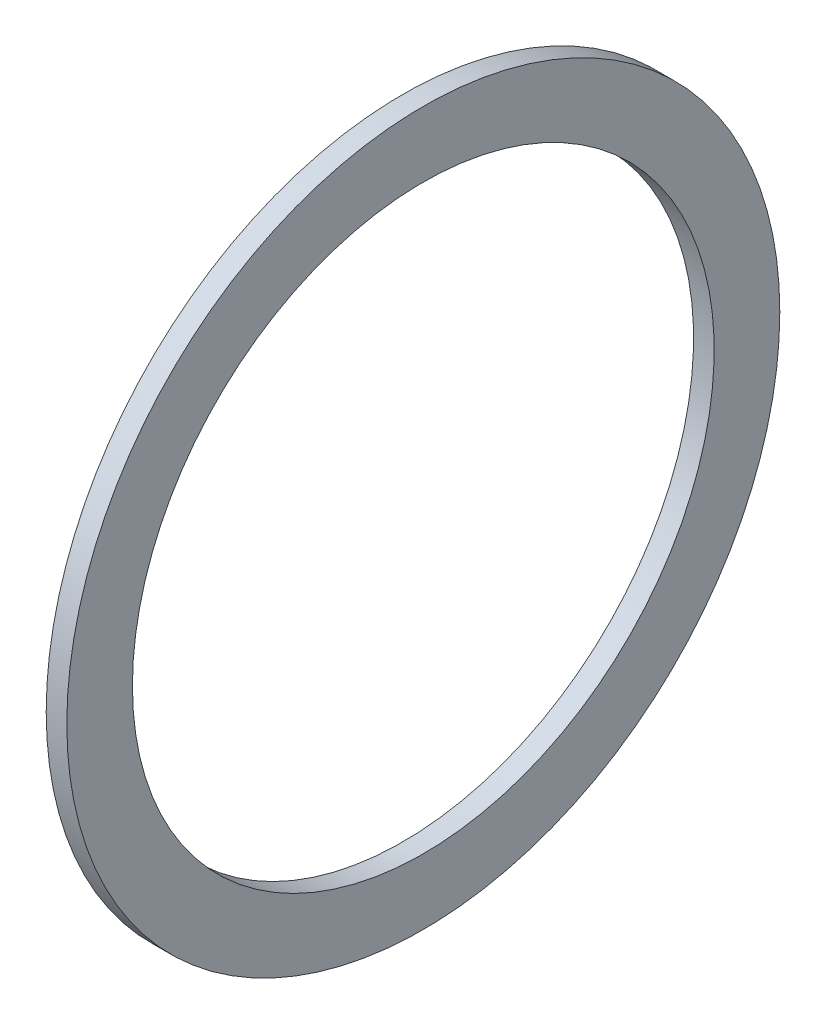
SolidWorks part; units mm, degrees
ref_plane "Front Plane" through (0, 0, 0) normal (0, 0, 1) x (1, 0, 0)
ref_plane "Top Plane" through (0, 0, 0) normal (0, 1, 0) x (1, 0, 0)
ref_plane "Right Plane" through (0, 0, 0) normal (1, 0, 0) x (0, 0, -1)
sketch "Sketch2" plane through (0, 0, 0) normal (0, 0, 1) x (1, 0, 0)
  line L0 (0, 0) -> (58.591, 0) construction
  line L2 (0, 0) -> (18.4, 0)
  line L3 (0, 0) -> (0, 2.5)
  line L4 (0, 2.5) -> (18.4, 2.5)
  line L5 (18.4, 0) -> (18.4, 2.5)
  line L6 (6.0094, 2.5) -> (6.0094, 6)
  line L11 (6.0094, 6) -> (9.9794, 6)
  line L16 (12.9794, 6) -> (12.9794, 3)
  line L17 (12.9794, 3) -> (13.6398, 3)
  line L18 (13.6398, 3) -> (13.6398, 2.5)
  line L19 (13.6398, 2.5) -> (6.0094, 2.5)
  line L22 (13.6398, 2.5) -> (16.1198, 2.5)
  line L23 (13.6398, 2.5) -> (13.6398, 4)
  line L24 (13.6398, 4) -> (16.1198, 4)
  line L25 (16.1198, 2.5) -> (16.1198, 4)
  line L27 (6.0094, 6) -> (9.9794, 6)
  line L28 (6.0094, 6) -> (6.0094, 9)
  line L29 (6.0094, 9) -> (9.9794, 9)
  line L30 (9.9794, 6) -> (9.9794, 9)
  line L31 (6.0094, 9) -> (6.0094, 8.25)
  line L32 (6.0094, 8.25) -> (5.0094, 8.25)
  line L33 (8.6609, 22.001) -> (8.6609, 12.476) construction
  line L34 (5.0094, 12.476) -> (12.3124, 12.476)
  line L35 (9.9794, 9) -> (12.3124, 9)
  line L36 (5.0094, 7.9375) -> (1.8344, 7.9375)
  line L37 (5.0094, 8.25) -> (5.0094, 12.476)
  line L38 (5.0094, 7.9375) -> (5.0094, 13.9365)
  line L39 (5.0094, 13.9365) -> (1.8344, 13.9365)
  line L40 (1.8344, 7.9375) -> (1.8344, 13.9365)
  line L41 (5.0094, 22.001) -> (12.3124, 22.001)
  line L42 (5.0094, 22.001) -> (5.0094, 30.1625)
  line L43 (5.0094, 30.1625) -> (12.3124, 30.1625)
  line L44 (12.3124, 22.001) -> (12.3124, 30.1625)
  line L49 (16.6398, 22.001) -> (16.6398, 7.5)
  line L51 (23.0198, 7.5) -> (23.0198, 6.5)
  line L54 (16.1198, 4) -> (13.6398, 4)
  line L56 (18.0398, 7.5) -> (23.0198, 7.5)
  line L57 (13.3124, 22.001) -> (16.6398, 22.001)
  line L58 (16.1198, 3.5) -> (20.0198, 3.5)
  line L59 (29.9098, 14) -> (26.9098, 11)
  line L60 (4.0094, 31.75) -> (18.0398, 31.75)
  line L61 (18.0398, 7.5) -> (23.0198, 7.5)
  line L62 (18.0398, 7.5) -> (18.0398, 12)
  line L63 (18.0398, 12) -> (23.0198, 12)
  line L64 (23.0198, 7.5) -> (23.0198, 12)
  line L65 (18.0398, 31.75) -> (18.0398, 12)
  line L66 (23.0198, 11) -> (26.9098, 11)
  line L67 (34.8098, 23) -> (31.3098, 19.5)
  line L68 (35.8098, 31) -> (38.7998, 33.99)
  line L69 (29.9098, 14) -> (29.9098, 15)
  line L70 (29.9098, 15) -> (22.9398, 15)
  line L71 (22.9398, 15) -> (21.0398, 15)
  line L72 (18.0398, 7.5) -> (16.6398, 7.5)
  line L73 (21.0398, 15) -> (21.0398, 43)
  line L74 (19.5798, 40) -> (9.6198, 40)
  line L75 (9.6198, 40) -> (4.0094, 40)
  line L76 (21.0398, 43) -> (19.5798, 43)
  line L77 (22.9398, 15) -> (29.9098, 15)
  line L78 (22.9398, 15) -> (22.9398, 21)
  line L79 (22.9398, 21) -> (29.9098, 21)
  line L80 (29.9098, 15) -> (29.9098, 21)
  line L81 (9.6198, 40) -> (19.5798, 40)
  line L82 (9.6198, 40) -> (9.6198, 50)
  line L83 (9.6198, 50) -> (19.5798, 50)
  line L84 (19.5798, 40) -> (19.5798, 50)
  line L85 (4.0094, 40) -> (4.0094, 31.75)
  line L86 (12.9794, 3) -> (12.9794, 2.5)
  line L87 (31.3098, 19.5) -> (29.9098, 19.5)
  line L88 (21.4694, 63.5) -> (21.4694, 51.308)
  line L89 (21.4694, 63.5) -> (25.9398, 63.5)
  line L90 (25.9398, 63.5) -> (25.9398, 25)
  line L91 (27.8398, 25) -> (25.9398, 25)
  line L92 (9.6198, 48) -> (8.1598, 48)
  line L93 (8.1598, 48) -> (8.1598, 53.476)
  line L94 (8.1598, 53.476) -> (19.5798, 53.476)
  line L95 (19.5798, 53.476) -> (19.5798, 50)
  line L96 (13.8698, 63.001) -> (13.8698, 53.476) construction
  line L97 (8.1598, 63.001) -> (19.5798, 63.001)
  line L98 (8.1598, 63.001) -> (8.1598, 68.2625)
  line L99 (8.1598, 68.2625) -> (19.5798, 68.2625)
  line L100 (19.5798, 63.001) -> (19.5798, 68.2625)
  line L101 (12.9794, 6) -> (11.9794, 6)
  line L102 (8.1598, 44.825) -> (4.9848, 44.825)
  line L103 (8.1598, 44.825) -> (8.1598, 54.9365)
  line L104 (8.1598, 54.9365) -> (4.9848, 54.9365)
  line L106 (9.9794, 6) -> (10.8794, 6)
  line L107 (27.8398, 25) -> (34.8098, 25)
  line L108 (34.8098, 25) -> (34.8098, 23)
  line L109 (0, 0) -> (-2, 0)
  line L110 (0, 0) -> (0, 11)
  line L111 (27.8398, 25) -> (34.8098, 25)
  line L112 (27.8398, 25) -> (27.8398, 32.5)
  line L113 (27.8398, 32.5) -> (34.8098, 32.5)
  line L114 (34.8098, 25) -> (34.8098, 32.5)
  line L115 (35.8098, 31) -> (34.8098, 31)
  line L116 (27.8398, 32.5) -> (27.8398, 64.5)
  line L117 (20.5373, 74.025) -> (6.2023, 74.025)
  line L118 (6.2023, 74.025) -> (6.2023, 76.2)
  line L119 (38.7998, 47.29) -> (30.8398, 55.25)
  line L120 (0, 11) -> (-2, 11)
  line L121 (38.7998, 43.815) -> (30.8623, 43.815)
  line L123 (-4.8152, 69.85) -> (1.5348, 76.2)
  line L124 (38.7998, 47.29) -> (38.7998, 33.99)
  line L125 (-2, 0) -> (-2, 11)
  line L126 (38.7998, 37.465) -> (30.8623, 37.465)
  line L127 (30.8623, 43.815) -> (30.8623, 37.465)
  line L128 (6.0094, 2.5) -> (6.0094, 0)
  line L129 (-0.0152, 63.5) -> (-0.0152, 30)
  line L132 (4.9848, 63.5) -> (-0.0152, 63.5)
  line L136 (-1.8152, 30) -> (-11.7752, 30)
  line L138 (-13.7752, 25.4) -> (-2, 25.4)
  line L139 (-2, 25.4) -> (-2, 11.5)
  line L140 (27.8398, 64.5) -> (20.5373, 64.5)
  line L141 (-1.8152, 30) -> (-11.7752, 30)
  line L142 (-1.8152, 30) -> (-1.8152, 39)
  line L143 (-1.8152, 39) -> (-11.7752, 39)
  line L144 (-11.7752, 30) -> (-11.7752, 39)
  line L145 (20.5373, 64.5) -> (20.5373, 74.025)
  line L146 (-12.7752, 37) -> (-12.7752, 47.29)
  line L147 (-12.7752, 37) -> (-11.7752, 37)
  line L148 (30.8398, 55.25) -> (30.8398, 76.2)
  line L149 (11.9794, 6) -> (11.9794, 5.45)
  line L154 (-2, 11.5) -> (0.5, 11.5)
  line L155 (4.9848, 60.6197) -> (24.0348, 60.6197)
  line L160 (4.9848, 60.6197) -> (4.9848, 55.8572)
  line L161 (4.9848, 55.8572) -> (24.0348, 55.8572)
  line L166 (24.0348, 60.6197) -> (24.0348, 55.8572)
  line L167 (4.9848, 60.6197) -> (24.0348, 55.8572) construction
  line L172 (4.9848, 55.8572) -> (24.0348, 60.6197) construction
  line L173 (24.0348, 62.2072) -> (25.9398, 62.2072)
  line L174 (11.9794, 5.45) -> (10.8794, 5.45)
  line L175 (10.8794, 6) -> (10.8794, 5.45)
  line L176 (24.0348, 62.2072) -> (24.0348, 54.2697)
  line L177 (24.0348, 54.2697) -> (25.9398, 54.2697)
  line L178 (25.9398, 62.2072) -> (25.9398, 54.2697)
  line L179 (24.0348, 62.2072) -> (25.9398, 54.2697) construction
  line L180 (24.0348, 54.2697) -> (25.9398, 62.2072) construction
  line L181 (3, 19.6197) -> (15.7, 19.6197)
  line L182 (3, 19.6197) -> (3, 14.8572)
  line L183 (3, 14.8572) -> (15.7, 14.8572)
  line L184 (15.7, 19.6197) -> (15.7, 14.8572)
  line L185 (3, 19.6197) -> (15.7, 14.8572) construction
  line L186 (3, 14.8572) -> (15.7, 19.6197) construction
  line L187 (15.7, 21.2072) -> (16.6398, 21.2072)
  line L188 (15.7, 21.2072) -> (15.7, 13.2697)
  line L189 (15.7, 13.2697) -> (16.6398, 13.2697)
  line L190 (16.6398, 21.2072) -> (16.6398, 13.2697)
  line L191 (15.7, 21.2072) -> (16.6398, 13.2697) construction
  line L192 (15.7, 13.2697) -> (16.6398, 21.2072) construction
  line L193 (0.5, 11.5) -> (0.5, 6.9375)
  line L194 (0.5, 6.9375) -> (1.8344, 6.9375)
  line L195 (23.0198, 6.5) -> (20.0198, 3.5)
  line L196 (4.9848, 63.5) -> (4.9848, 54.9365)
  line L197 (3, 43.825) -> (4.9848, 43.825)
  line L198 (1.8344, 6.9375) -> (1.8344, 7.9375)
  line L199 (6.0094, 0) -> (12.9794, 0)
  line L200 (12.9794, 0) -> (12.9794, 2.5)
  line L201 (18.0398, 31.75) -> (18.0398, 35.875)
  line L202 (18.0398, 35.875) -> (21.0398, 35.875)
  line L203 (30.8398, 76.2) -> (6.2023, 76.2)
  line L204 (2.7573, 69.85) -> (7.2023, 69.85) construction
  line L205 (7.2023, 67.4688) -> (26.2523, 67.4688)
  line L206 (7.2023, 74.025) -> (7.2023, 64.5)
  line L207 (7.2023, 64.5) -> (-1.8152, 64.5)
  line L208 (-1.8152, 64.5) -> (-1.8152, 39)
  line L209 (-12.7752, 47.29) -> (-4.8152, 55.25)
  line L210 (-4.8152, 55.25) -> (-4.8152, 69.85)
  line L211 (7.2023, 67.4688) -> (7.2023, 72.2312)
  line L212 (7.2023, 72.2312) -> (26.2523, 72.2313)
  line L213 (26.2523, 67.4688) -> (26.2523, 72.2313)
  line L214 (26.2523, 73.8187) -> (30.8398, 73.8187)
  line L215 (26.2523, 73.8187) -> (26.2523, 65.8813)
  line L216 (26.2523, 65.8813) -> (30.8398, 65.8813)
  line L217 (30.8398, 73.8187) -> (30.8398, 65.8813)
  line L218 (2.7573, 72.2313) -> (24.9823, 72.2313)
  line L219 (2.7573, 72.2313) -> (2.7573, 67.4687)
  line L220 (2.7573, 67.4687) -> (24.9823, 67.4687)
  line L221 (24.9823, 72.2313) -> (24.9823, 67.4687)
  line L222 (24.9823, 69.85) -> (20.5373, 69.85) construction
  line L223 (21.4694, 51.308) -> (22.9398, 51.308)
  line L224 (22.9398, 51.308) -> (22.9398, 21)
  line L225 (13.6398, 4) -> (13.6398, 12.2697)
  line L226 (13.6398, 12.2697) -> (13.3124, 12.2697)
  line L227 (13.3124, 12.2697) -> (13.3124, 22.001)
  line L228 (12.3124, 9) -> (12.3124, 12.476)
  line L229 (-1.8152, 30) -> (-0.0152, 30)
  line L230 (8.1598, 65.6317) -> (2.7573, 65.6317) construction
  line L231 (19.5798, 65.6317) -> (24.9823, 65.6317) construction
  line L232 (1.5348, 76.2) -> (6.2023, 76.2)
  line L233 (-11.7752, 30) -> (-13.7752, 30)
  line L234 (-13.7752, 30) -> (-13.7752, 25.4)
  line L235 (3, 13.9365) -> (3, 43.825)
  line L236 (4.9848, 54.9365) -> (4.9848, 44.825)
  line L237 (4.9848, 43.825) -> (4.9848, 44.825)
  circle A0 centre (26.8898, 25.95) radius 0.95
  circle A1 centre (21.9898, 15.95) radius 0.95
  circle A2 centre (17.3398, 8.2) radius 0.7
  circle A3 centre (10.4294, 6.45) radius 0.45
  circle A4 centre (-0.9152, 30.9) radius 0.9
  point P7 (24.9873, 58.2385)
  point P131 (16.1699, 17.2385)
  point P135 (14.5098, 58.2385)
  point P146 (9.35, 17.2385)
sketch "Sketch3" plane through (0, 0, 0) normal (0, 0, 1) x (1, 0, 0)
  line L0 (8.1598, 44.825) -> (8.1598, 54.9365) construction
  line L1 (8.1598, 54.9365) -> (4.9848, 54.9365) construction
  line L3 (8.1598, 44.825) -> (4.9848, 44.825) construction
  line L4 (8.1598, 44.825) -> (8.1598, 54.9365)
  line L5 (8.1598, 54.9365) -> (4.9848, 54.9365)
  line L7 (8.1598, 44.825) -> (4.9848, 44.825)
  line L8 (4.9848, 54.9365) -> (4.9848, 44.825) construction
  line L9 (4.9848, 54.9365) -> (4.9848, 44.825)
revolve "Revolve1" add sketch "Sketch3" angle 360 about L0
